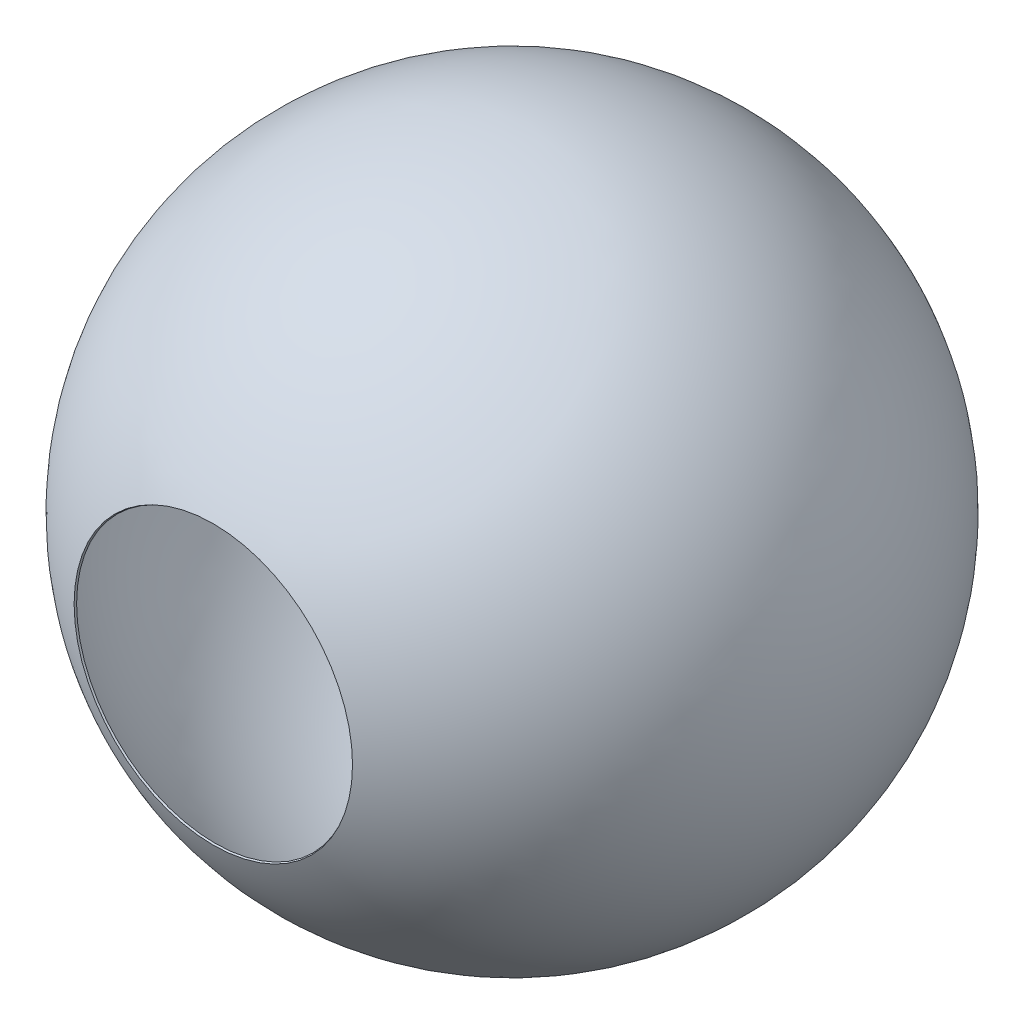
SolidWorks part; units mm, degrees
ref_plane "Front Plane" through (0, 0, 0) normal (0, 0, 1) x (1, 0, 0)
ref_plane "Top Plane" through (0, 0, 0) normal (0, 1, 0) x (1, 0, 0)
ref_plane "Right Plane" through (0, 0, 0) normal (1, 0, 0) x (0, 0, -1)
sketch "Sketch1" plane through (0, 0, 0) normal (1, 0, 0) x (0, 0, -1)
  line L0 (528.5016, 124.6399) -> (528.5016, 0)
  line L3 (-495, 230.6517) -> (-495, 0) construction
  line L4 (-492.1901, 229.3424) -> (0, 0) construction
  line L5 (-495, 230.6517) -> (-492.1901, 229.3424)
  line L6 (-495, 0) -> (531.6016, 0) construction
  line L7 (531.6016, 125) -> (531.6016, 0)
  line L8 (528.5016, 0) -> (531.6016, 0)
  arc A0 (531.6016, 125) -> (-495, 230.6517) centre (0, 0) ccw
  arc A1 (528.5016, 124.6399) -> (-492.1901, 229.3424) centre (0, 0) ccw
  dimension "D2" = 543
  dimension "D3" = 495
  dimension "D4" = 125
  dimension "D5" = 3.1
  dimension "PressureHull_InnerRadius" = 546.1
revolve "Shell" add sketch "Sketch1" angle 360 about L6
sketch "Picture Sketch" plane through (0, 0, 0) normal (0, 0, 1) x (1, 0, 0)
  line L0 (-356.5753, -20.7815) -> (269.657, 26.3052) construction
  line L1 (0, 543) -> (0, -543) construction
  line L2 (0, 0) -> (271.5, 470.2518) construction
  line L3 (0, 0) -> (-271.5, 470.2518) construction
  line L4 (-543, 0) -> (543, 0) construction
  line L5 (0, 0) -> (457.9616, -291.7537) construction
  line L6 (0, 0) -> (-457.9616, -291.7537) construction
  circle A0 centre (0, 0) radius 543
  dimension "D1" = 1086
  dimension "D2" = 60
  dimension "D3" = 115
equation "\"PressureHull_InnerRadius\"= 546.1mm"
equation "\"PressureHull_OuterRadius\"= 609.6mm"
equation "\"InnerShell_InnerRadius\"= 543mm"
